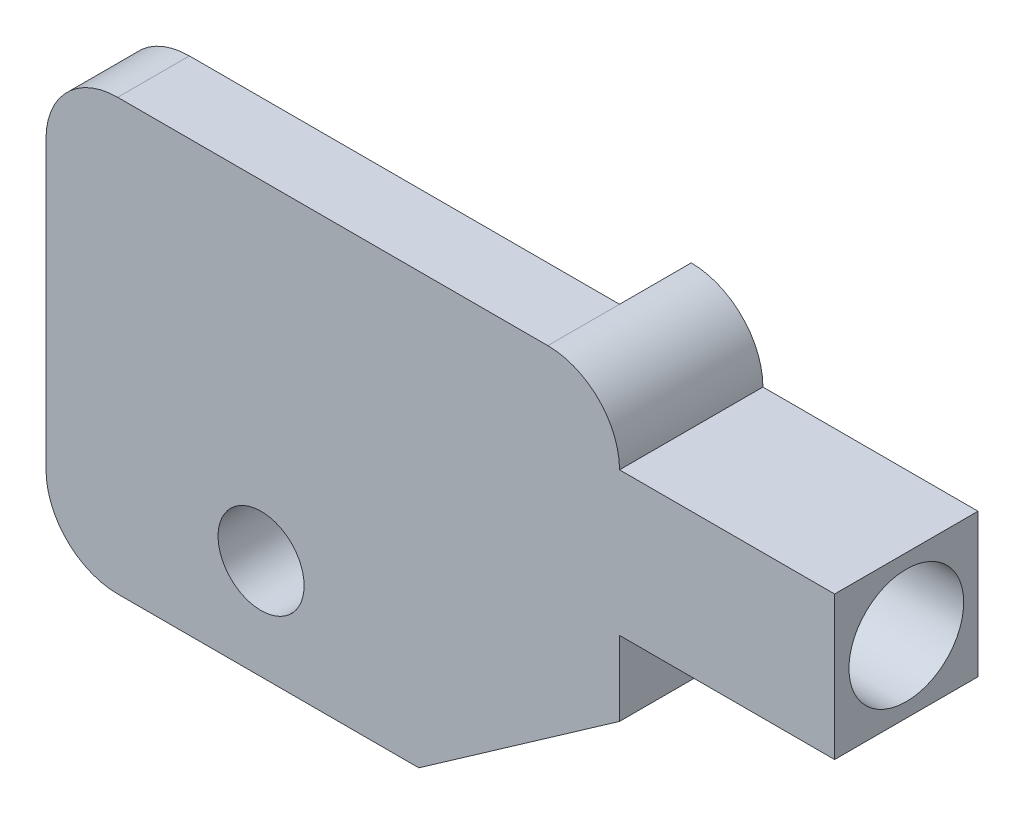
SolidWorks part; units mm, degrees
ref_plane "Front Plane" through (0, 0, 0) normal (0, 0, 1) x (1, 0, 0)
ref_plane "Top Plane" through (0, 0, 0) normal (0, 1, 0) x (1, 0, 0)
ref_plane "Right Plane" through (0, 0, 0) normal (1, 0, 0) x (0, 0, -1)
sketch "Sketch2" plane through (0, 0, 0) normal (0, 0, 1) x (1, 0, 0)
  line L1 (25.4, -19.05) -> (-25.4, -19.05)
  line L2 (25.4, -19.05) -> (25.4, 19.05)
  line L3 (25.4, 19.05) -> (-25.4, 19.05)
  line L4 (-25.4, -19.05) -> (-25.4, 19.05)
  line L5 (25.4, -19.05) -> (-25.4, 19.05) construction
  line L6 (25.4, 19.05) -> (-25.4, -19.05) construction
  point P0 (0, 0)
  dimension "D1" = 38.1
  dimension "D2" = 50.8
extrude "Boss-Extrude1" add sketch "Sketch2" along normal blind 12.7
fillet "Fillet1" radius 6.35 3 edges at (-25.4, -19.05, 6.35) (-25.4, 19.05, 6.35) (25.4, 19.05, 6.35)
sketch "Sketch3" plane through (0, 0, 12.7) normal (0, 0, 1) x (1, 0, 0)
  line L0 (-25.4, 12.7) -> (-25.4, -12.7) construction
  line L1 (19.05, 19.05) -> (-19.05, 19.05) construction
  circle A0 centre (-6.35, -10.16) radius 3.81
  dimension "D1" = 7.62
  dimension "D2" = 19.05
  dimension "D3" = 29.21
extrude "Cut-Extrude1" cut sketch "Sketch3" against normal through all
sketch "Sketch7" plane through (25.4, 0, 0) normal (1, 0, 0) x (0, 0, -1)
  line L1 (-12.7, 0) -> (0, 0)
  line L2 (-12.7, 0) -> (-12.7, 12.7)
  line L3 (-12.7, 12.7) -> (0, 12.7)
  line L4 (0, 0) -> (0, 12.7)
  dimension "D1" = 12.7
extrude "Boss-Extrude2" add sketch "Sketch7" along normal blind 19.05
sketch "Sketch8" plane through (44.45, 0, 0) normal (1, 0, 0) x (0, 0, -1)
  line L0 (-12.7, 12.7) -> (-12.7, 0) construction
  line L1 (-12.7, 0) -> (0, 0) construction
  circle A0 centre (-6.35, 6.35) radius 5.08
  dimension "D3" = 10.16
  dimension "D1" = 6.35
  dimension "D2" = 6.35
extrude "Cut-Extrude2" cut sketch "Sketch8" against normal blind 25.4
sketch "Sketch9" plane through (-25.4, 0, 0) normal (-1, 0, 0) x (0, 0, 1)
  line L0 (0, 19.05) -> (12.7, 19.05) construction
  line L1 (0, -19.05) -> (6.35, -19.05)
  line L2 (0, -19.05) -> (0, 19.05)
  line L3 (0, 19.05) -> (6.35, 19.05)
  line L4 (6.35, -19.05) -> (6.35, 19.05)
extrude "Cut-Extrude3" cut sketch "Sketch9" against normal blind 44.45
sketch "Sketch10" plane through (19.05, 0, 0) normal (-1, 0, 0) x (0, 0, 1)
  line L1 (6.35, -12.7) -> (0, -12.7)
  line L2 (6.35, -12.7) -> (6.35, -19.05)
  line L3 (6.35, -19.05) -> (0, -19.05)
  line L4 (0, -12.7) -> (0, -19.05)
  dimension "D1" = 6.35
  dimension "D2" = 6.35
extrude "Cut-Extrude4" cut sketch "Sketch10" against normal up to next
chamfer "Chamfer6" distance 17.78 angle 35 1 edges at (25.4, -19.05, 9.525) first distance on face at (3.175, -19.05, 9.525)
